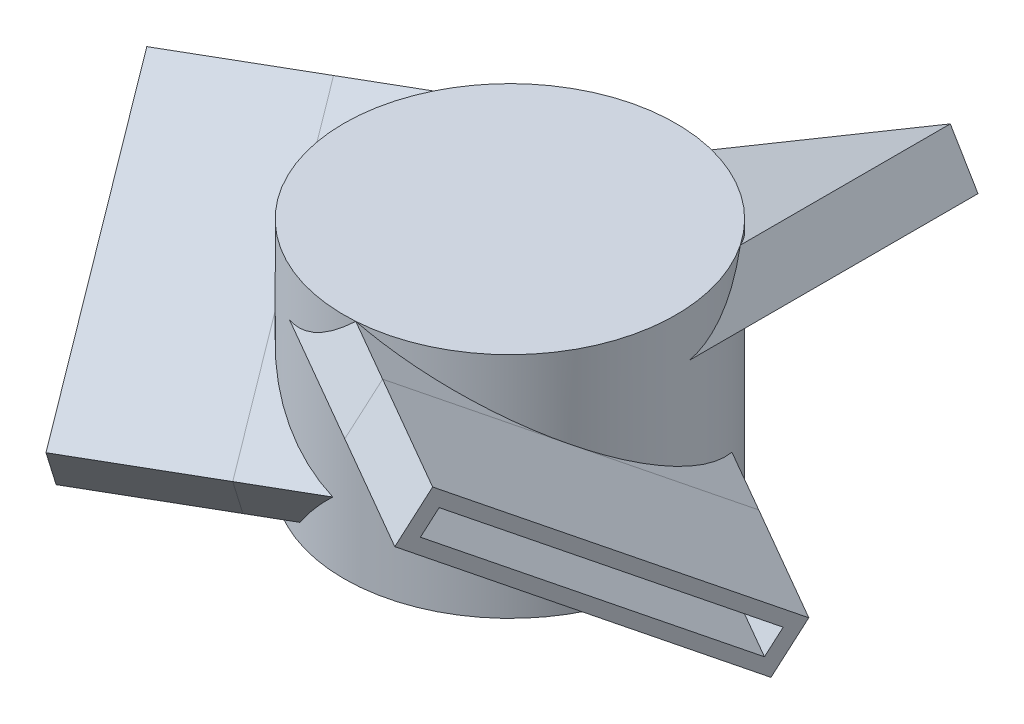
SolidWorks part; units mm, degrees
ref_plane "Front Plane" through (0, 0, 0) normal (0, 0, 1) x (1, 0, 0)
ref_plane "Top Plane" through (0, 0, 0) normal (0, 1, 0) x (1, 0, 0)
ref_plane "Right Plane" through (0, 0, 0) normal (1, 0, 0) x (0, 0, -1)
sketch "Diametre root" plane through (0, 0, 0) normal (0, 0, 1) x (1, 0, 0)
  line L0 (0, 0) -> (0, -120)
  line L1 (0, 0) -> (-103.923, 60)
  line L2 (0, 0) -> (103.923, 60)
  circle A0 centre (0, 0) radius 120
  dimension "D1" = 240
  dimension "D2" = 120
  dimension "D3" = 120
sketch "Sketch2" plane through (0, 0, 0) normal (0, 0, 1) x (1, 0, 0)
  line L0 (7.0111, -39.2783) -> (135.9622, 37.3481)
  line L1 (135.9622, 37.3481) -> (142.9889, 25.5233)
  line L2 (142.9889, 25.5233) -> (14.0378, -51.1031)
  line L3 (14.0378, -51.1031) -> (7.0111, -39.2783)
  line L4 (75, 0) -> (75, -191.2717) construction
  line L5 (75, 0) -> (75, -13.755) construction
  line L6 (75, -6.8775) -> (-0.2232, 119.7121) construction
  point P9 (75, -6.8775)
  dimension "D1" = 150
  dimension "D2" = 13.755
  dimension "D3" = 30.72
extrude "Extrude-Thin1" add sketch "Sketch2" along normal blind 70 thin thin type one direction wall 7
ref_plane "Plane2" through (15.5031, -26.0895, 0) normal (-0.5108, 0.8597, 0) x (0.8597, 0.5108, 0)
sketch "Sketch3" plane through (8.3365, 0, 0) normal (0, 1, 0) x (1, 0, 0)
  line L0 (130.0676, -70) -> (-10.919, -70) construction
  line L1 (130.0676, -70) -> (-10.919, -70)
  line L2 (59.5743, -155) -> (59.5743, -70) construction
  circle A0 centre (59.5743, -155) radius 85
  dimension "D1" = 170
  dimension "D2" = 85
extrude "Boss-Extrude2" add sketch "Sketch3" against normal blind 70 and the other way up to vertex (46.9418 mm away) separate body contours A0 region at (67.9108, 0, 155) other way up to point (138.404, 46.9418, 70)
ref_axis "Axis1" through (67.9108, 181.6285, 155) along (0, 1, 0)
pattern_circular "CirPattern1" count 3 over 360 about axis through (67.9108, 181.6285, 155) along (0, 1, 0) of bodies 102
sketch "Sketch4" plane through (0, 0, 70) normal (0, 0, 1) x (1, 0, 0)
  line L0 (138.404, 46.9418) -> (152.5825, 23.0815)
  line L1 (152.5825, 23.0815) -> (11.596, -60.6968)
  line L2 (11.596, -60.6968) -> (-2.5825, -36.8365)
  line L3 (-2.5825, -36.8365) -> (138.404, 46.9418)
ref_plane "Plane3" through (0, 0, 120) normal (0, 0, 1) x (1, 0, 0)
sketch "Sketch8" plane through (0, 0, 70) normal (0, 0, 1) x (1, 0, 0)
  line L0 (11.596, -60.6968) -> (-2.5825, -36.8365)
  line L1 (-2.5825, -36.8365) -> (138.404, 46.9418)
  line L2 (138.404, 46.9418) -> (152.5825, 23.0815)
  line L3 (152.5825, 23.0815) -> (11.596, -60.6968)
  point P4 (22.2501, -30.6625)
extrude "Boss-Extrude6" add sketch "Sketch8" along normal blind 85
pattern_circular "CirPattern5" count 3 over 360 about axis through (67.9108, 181.6285, 155) along (0, 1, 0) of "Boss-Extrude6"
equation "\"D2@Sketch2\"=\"D1@Sketch2\"*0.0917"
